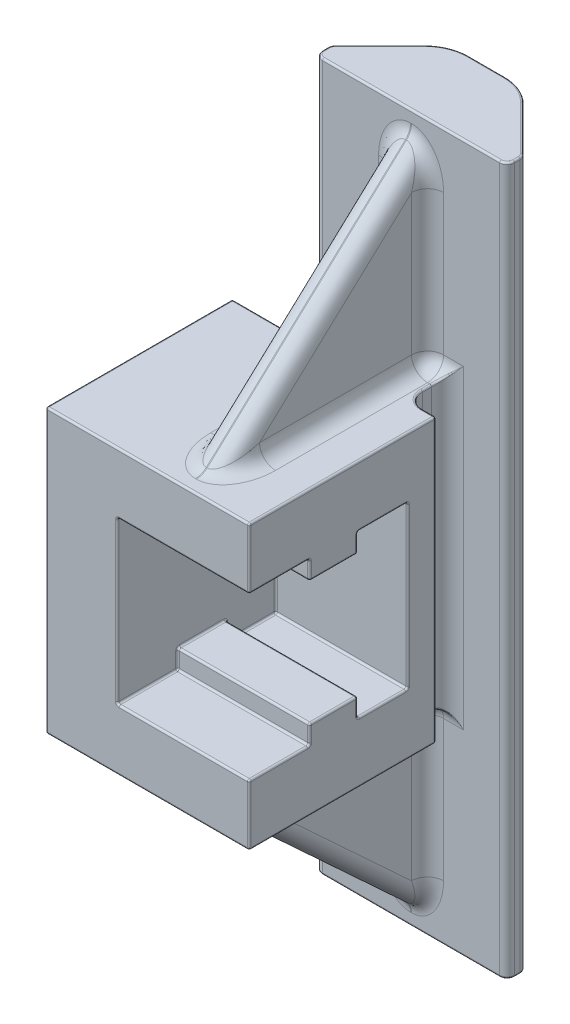
SolidWorks part; units mm, degrees
ref_plane "Front Plane" through (0, 0, 0) normal (0, 0, 1) x (1, 0, 0)
ref_plane "Top Plane" through (0, 0, 0) normal (0, 1, 0) x (1, 0, 0)
ref_plane "Right Plane" through (0, 0, 0) normal (1, 0, 0) x (0, 0, -1)
sketch "Sketch15" plane through (0, 0, 0) normal (0, 1, 0) x (1, 0, 0)
  line L0 (-3.964, 1.5536) -> (-3.964, 2.5104) construction
  line L1 (-5.6176, 4.164) -> (-9.3853, 4.164)
  line L2 (-10.187, 4.9657) -> (-10.187, 5.534)
  line L3 (-9.9522, 6.1008) -> (-5.2214, 10.8317)
  line L4 (-1.9335, 12.1936) -> (1.9335, 12.1936)
  line L5 (5.2214, 10.8317) -> (9.9522, 6.1008)
  line L6 (10.187, 5.534) -> (10.187, 4.9657)
  line L7 (9.3853, 4.164) -> (5.6176, 4.164)
  line L8 (3.964, 2.5104) -> (3.964, 1.5536) construction
  line L9 (-5.6176, 4.164) -> (5.6176, 4.164)
  line L130 (-14.3277, 0) -> (-9.4961, 0) construction
  line L131 (-7.9763, 0) -> (-5.6176, 0) construction
  line L132 (-4.064, 1.5536) -> (-4.064, 2.5104) construction
  line L133 (-5.6176, 4.064) -> (-9.3853, 4.064) construction
  line L134 (-10.287, 4.9657) -> (-10.287, 5.534) construction
  line L135 (-10.0229, 6.1716) -> (-5.2921, 10.9024) construction
  line L136 (-1.9335, 12.2936) -> (1.9335, 12.2936) construction
  line L137 (5.2921, 10.9024) -> (10.0229, 6.1716) construction
  line L138 (10.287, 5.534) -> (10.287, 4.9657) construction
  line L139 (9.3853, 4.064) -> (5.6176, 4.064) construction
  line L140 (4.064, 2.5104) -> (4.064, 1.5536) construction
  line L141 (5.6176, 0) -> (7.9763, 0) construction
  line L142 (9.4961, 0) -> (14.3277, 0) construction
  arc A0 (-5.6176, -0.1) -> (-3.964, 1.5536) centre (-5.6176, 1.5536) ccw construction
  arc A1 (-3.964, 2.5104) -> (-5.6176, 4.164) centre (-5.6176, 2.5104) ccw construction
  arc A2 (-10.187, 4.9657) -> (-9.3853, 4.164) centre (-9.3853, 4.9657) ccw
  arc A3 (-9.9522, 6.1008) -> (-10.187, 5.534) centre (-9.3853, 5.534) ccw
  arc A4 (-1.9335, 12.1936) -> (-5.2214, 10.8317) centre (-1.9335, 7.5438) ccw
  arc A5 (5.2214, 10.8317) -> (1.9335, 12.1936) centre (1.9335, 7.5438) ccw
  arc A6 (10.187, 5.534) -> (9.9522, 6.1008) centre (9.3853, 5.534) ccw
  arc A7 (9.3853, 4.164) -> (10.187, 4.9657) centre (9.3853, 4.9657) ccw
  arc A8 (5.6176, 4.164) -> (3.964, 2.5104) centre (5.6176, 2.5104) ccw construction
  arc A9 (3.964, 1.5536) -> (5.6176, -0.1) centre (5.6176, 1.5536) ccw construction
  arc A151 (-19.05, 3.2025) -> (-15.8475, 0) centre (-15.8751, 3.1749) ccw construction
  arc A152 (-14.3277, 0) -> (-15.8475, 0) centre (-15.0876, 0.0567) ccw construction
  arc A153 (-7.9763, 0) -> (-9.4961, 0) centre (-8.7362, 0.0567) ccw construction
  arc A154 (-5.6176, 0) -> (-4.064, 1.5536) centre (-5.6176, 1.5536) ccw construction
  arc A155 (-4.064, 2.5104) -> (-5.6176, 4.064) centre (-5.6176, 2.5104) ccw construction
  arc A156 (-10.287, 4.9657) -> (-9.3853, 4.064) centre (-9.3853, 4.9657) ccw construction
  arc A157 (-10.0229, 6.1716) -> (-10.287, 5.534) centre (-9.3853, 5.534) ccw construction
  arc A158 (-1.9335, 12.2936) -> (-5.2921, 10.9024) centre (-1.9335, 7.5438) ccw construction
  arc A159 (5.2921, 10.9024) -> (1.9335, 12.2936) centre (1.9335, 7.5438) ccw construction
  arc A160 (10.287, 5.534) -> (10.0229, 6.1716) centre (9.3853, 5.534) ccw construction
  arc A161 (9.3853, 4.064) -> (10.287, 4.9657) centre (9.3853, 4.9657) ccw construction
  arc A162 (5.6176, 4.064) -> (4.064, 2.5104) centre (5.6176, 2.5104) ccw construction
  arc A163 (4.064, 1.5536) -> (5.6176, 0) centre (5.6176, 1.5536) ccw construction
  arc A164 (9.4961, 0) -> (7.9763, 0) centre (8.7362, 0.0567) ccw construction
  point P0 (11.9119, 0)
  dimension "D1" = 0.1
extrude "Boss-Extrude6" add sketch "Sketch15" along normal mid plane 75
sketch "Sketch1" plane through (0, 0, 0) normal (0, 1, 0) x (1, 0, 0)
  line L0 (-14.5877, -0.2) -> (-14.5877, -20)
  line L5 (7, -0.2) -> (7, -20)
  line L6 (5.6176, -0.2) -> (8.2363, -0.2) construction
  line L7 (-14.5877, -20) -> (7, -20)
  line L8 (-5.6176, -0.2) -> (-3.864, -0.2)
  line L9 (-3.864, -0.2) -> (-3.864, 1.5536)
  line L10 (-3.864, 2.5104) -> (-3.864, 5)
  line L11 (3.864, 1.5536) -> (3.864, -0.2)
  line L12 (3.864, 2.5104) -> (3.864, 5)
  line L13 (3.864, -0.2) -> (5.6176, -0.2)
  line L14 (-14.3277, 0) -> (-9.4961, 0) construction
  line L16 (5.6176, 0) -> (7.9763, 0) construction
  line L17 (4.064, 2.5104) -> (4.064, 1.5536) construction
  line L18 (9.3853, 4.064) -> (5.6176, 4.064) construction
  line L19 (-7.9763, 0) -> (-5.6176, 0) construction
  line L20 (-4.064, 1.5536) -> (-4.064, 2.5104) construction
  line L21 (-5.6176, 4.064) -> (-9.3853, 4.064) construction
  line L22 (-14.5877, -0.2) -> (-9.2361, -0.2)
  line L23 (-8.2363, -0.2) -> (-5.6176, -0.2)
  line L24 (-3.864, 1.5536) -> (-3.864, 2.5104)
  line L27 (3.864, 2.5104) -> (3.864, 1.5536)
  line L28 (5.6176, -0.2) -> (7, -0.2)
  line L30 (9.3853, 4.264) -> (5.6176, 4.264) construction
  line L31 (-5.6176, 4.264) -> (-9.3853, 4.264) construction
  line L32 (3.864, 5) -> (-3.864, 5)
  line L35 (9.2361, -0.2) -> (14.5877, -0.2) construction
  line L36 (9.4961, 0) -> (14.3277, 0) construction
  arc A0 (-8.2363, -0.2) -> (-9.2361, -0.2) centre (-8.7362, -0.2) ccw
  arc A10 (-19.05, 3.2025) -> (-15.8475, 0) centre (-15.8751, 3.1749) ccw construction
  arc A11 (-14.3277, 0) -> (-15.8475, 0) centre (-15.0876, 0.0567) ccw construction
  arc A12 (-7.9763, 0) -> (-9.4961, 0) centre (-8.7362, 0.0567) ccw construction
  arc A15 (9.4961, 0) -> (7.9763, 0) centre (8.7362, 0.0567) ccw construction
  arc A16 (4.064, 1.5536) -> (5.6176, 0) centre (5.6176, 1.5536) ccw construction
  arc A17 (5.6176, 4.064) -> (4.064, 2.5104) centre (5.6176, 2.5104) ccw construction
  arc A18 (-5.6176, 0) -> (-4.064, 1.5536) centre (-5.6176, 1.5536) ccw construction
  arc A19 (-4.064, 2.5104) -> (-5.6176, 4.064) centre (-5.6176, 2.5104) ccw construction
  arc A23 (-5.6176, -0.2) -> (-3.864, 1.5536) centre (-5.6176, 1.5536) ccw construction
  arc A24 (-3.864, 2.5104) -> (-5.6176, 4.264) centre (-5.6176, 2.5104) ccw construction
  arc A25 (5.6176, 4.264) -> (3.864, 2.5104) centre (5.6176, 2.5104) ccw construction
  arc A26 (3.864, 1.5536) -> (5.6176, -0.2) centre (5.6176, 1.5536) ccw construction
  arc A30 (15.5934, -0.1883) -> (14.5877, -0.2) centre (15.0876, 0.0567) ccw construction
  arc A31 (15.5934, -0.1883) -> (19.25, 3.2043) centre (15.8751, 3.1749) ccw construction
  arc A32 (15.8475, 0) -> (19.05, 3.2025) centre (15.8751, 3.1749) ccw construction
  arc A33 (15.8475, 0) -> (14.3277, 0) centre (15.0876, 0.0567) ccw construction
  arc A34 (-19.25, 3.2043) -> (-15.5934, -0.1883) centre (-15.8751, 3.1749) ccw construction
  arc A35 (-14.5877, -0.2) -> (-15.5934, -0.1883) centre (-15.0876, 0.0567) ccw construction
  arc A36 (-8.2363, -0.2) -> (-9.2361, -0.2) centre (-8.7362, 0.0567) ccw construction
  arc A37 (9.2361, -0.2) -> (8.2363, -0.2) centre (8.7362, 0.0567) ccw construction
  point P0 (0, 0)
  dimension "D1" = 5
  dimension "D2" = 20
  dimension "D4" = 7
  dimension "D3" = 0.2
extrude "Boss-Extrude1" add sketch "Sketch1" along normal mid plane 30
sketch "Sketch12" plane through (7, 0, 0) normal (1, 0, 0) x (0, 0, -1)
  line L0 (-22.6, 8.55) -> (-22.6, -8.55)
  line L2 (-22.6, 8.55) -> (-13.6, 8.55)
  line L3 (-13.6, 8.55) -> (-13.6, 6.55)
  line L4 (-13.6, 6.55) -> (-8.5, 6.55)
  line L5 (-8.5, 6.55) -> (-8.5, 8.55)
  line L6 (-8.5, 8.55) -> (-3.2, 8.55)
  line L7 (-3.2, 8.55) -> (-3.2, -8.55)
  line L8 (-3.2, -8.55) -> (-8.5, -8.55)
  line L9 (-8.5, -8.55) -> (-8.5, -6.55)
  line L10 (-8.5, -6.55) -> (-13.6, -6.55)
  line L11 (-13.6, -6.55) -> (-13.6, -8.55)
  line L12 (-13.6, -8.55) -> (-22.6, -8.55)
  line L13 (-0.2, 0) -> (-22.6, 0) construction
  line L14 (-0.2, 15) -> (-0.2, -15) construction
  point P5 (-22.6, 0)
  dimension "D1" = 17.1
  dimension "D2" = 9
  dimension "D3" = 5.1
  dimension "D4" = 5.3
  dimension "D5" = 2
  dimension "D6" = 3.2
extrude "Cut-Extrude4" cut sketch "Sketch12" against normal blind 14
sketch "Sketch16" plane through (0, 0, 0) normal (1, 0, 0) x (0, 0, -1)
  line L0 (4.164, 37.5) -> (4.164, -37.5) construction
  line L1 (-0.2, 15) -> (4.164, 15) construction
  line L2 (-20, 15) -> (-0.2, 15) construction
  line L3 (4.164, 37.5) -> (4.164, -37.5) construction
  line L4 (-0.2, 15) -> (4.164, 15) construction
  line L5 (-20, 15) -> (-0.2, 15) construction
  line L6 (-18, 15) -> (4.164, 35.5)
  dimension "D1" = 2
  dimension "D2" = 2
rib "Rib1" sketch "Sketch16" sketch "Sketch16" thickness 3.5 extrusion direction parallel to sketch draft on no parameters "D1"=3.5
mirror "Mirror1" about plane through (0, 0, 0) normal (0, 1, 0) of "Rib1"
fillet "Fillet1" radius 1.7 24 edges at (0, -15, 18) (0, -35.5, -4.164) (-1.75, 15, 6.918) (1.75, -25.25, 6.918) (1.75, -15, 6.918) (1.75, -25.25, -4.164) (-1.75, -25.25, 6.918) (-1.75, -25.25, -4.164) (-1.75, -15, 6.918) (2.807, -15, -4.164) (-2.807, -15, -4.164) (-1.75, 25.25, 6.918) (1.75, 25.25, 6.918) (0, 15, 18) (1.75, 25.25, -4.164) (1.75, 15, 6.918) (2.807, 15, -4.164) (3.864, 0, -4.164) (3.864, 0, 0.2) (-3.864, 0, 0.2) (0, 35.5, -4.164) (-1.75, 25.25, -4.164) (-2.807, 15, -4.164) (-3.864, 0, -4.164)
fillet "Fillet2" radius 0.2 91 edges at (-8.7362, 15, -0.2999) (-8.7362, -15, -0.2999) (6.282, 15, 0.2) (4.3619, 15, -0.2979) (3.864, 15, -1.982) (4.3619, -15.4979, -3.6661) (3.864, -15, -1.982) (6.282, -15, 0.2) (-4.3619, 15.4979, -3.6661) (-3.864, 15, -1.982) (-6.9001, 15, 0.2) (-4.3619, -15.4979, -3.6661) (-3.864, -15, -1.982) (-4.3619, -15, -0.2979) (-7.5868, -37.5, -8.4663) (-10.126, -37.5, -5.8408) (-10.187, -37.5, -5.2498) (-9.9522, -37.5, -4.3988) (0, -37.5, -4.164) (9.9522, -37.5, -4.3988) (10.187, -37.5, -5.2498) (10.126, -37.5, -5.8408) (7.5868, -37.5, -8.4663) (3.7129, -37.5, -11.8397) (0, -37.5, -12.1936) (-3.7129, -37.5, -11.8397) (3.7129, 37.5, -11.8397) (7.5868, 37.5, -8.4663) (10.126, 37.5, -5.8408) (10.187, 37.5, -5.2498) (9.9522, 37.5, -4.3988) (0, 37.5, -4.164) (-9.9522, 37.5, -4.3988) (-10.187, 37.5, -5.2498) (-10.126, 37.5, -5.8408) (-7.5868, 37.5, -8.4663) (-3.7129, 37.5, -11.8397) (0, 37.5, -12.1936) (-9.2361, 0, 0.2) (-11.9119, 15, 0.2) (-11.9119, -15, 0.2) (-14.5877, 0, 0.2) (-14.5877, 15, 10.1) (-14.5877, -15, 10.1) (-3.7939, -15, 20) (-14.5877, 0, 20) (-3.7939, 15, 20) (7, -7.55, 8.5) (7, 8.55, 5.85) (7, 7.55, 8.5) (7, 11.775, 20) (7, 15, 10.1) (7, 0, 0.2) (7, -15, 10.1) (7, -11.775, 20) (7, -7.55, 13.6) (0, -8.55, 20) (0, -8.55, 13.6) (7, -8.55, 16.8) (0, -6.55, 13.6) (0, -6.55, 8.5) (7, -6.55, 11.05) (0, -8.55, 8.5) (7, -8.55, 5.85) (0, -8.55, 3.2) (0, 8.55, 3.2) (7, 0, 3.2) (0, 6.55, 8.5) (7, 6.55, 11.05) (0, 6.55, 13.6) (7, 7.55, 13.6) (0, 8.55, 13.6) (0, 8.55, 20) (7, 8.55, 16.8) (-7, 0, 20) (-7, 8.55, 16.8) (-7, 7.55, 13.6) (-7, 6.55, 11.05) (-7, 7.55, 8.5) (-7, 8.55, 5.85) (-7, 0, 3.2) (-7, -8.55, 5.85) (-7, -7.55, 8.5) (-7, -6.55, 11.05) (-7, -7.55, 13.6) (-7, -8.55, 16.8) (4.3619, 15.4979, -3.6661) (4.3619, -15, -0.2979) (-4.3619, 15, -0.2979) (-6.9001, -15, 0.2) (0, 8.55, 8.5)
